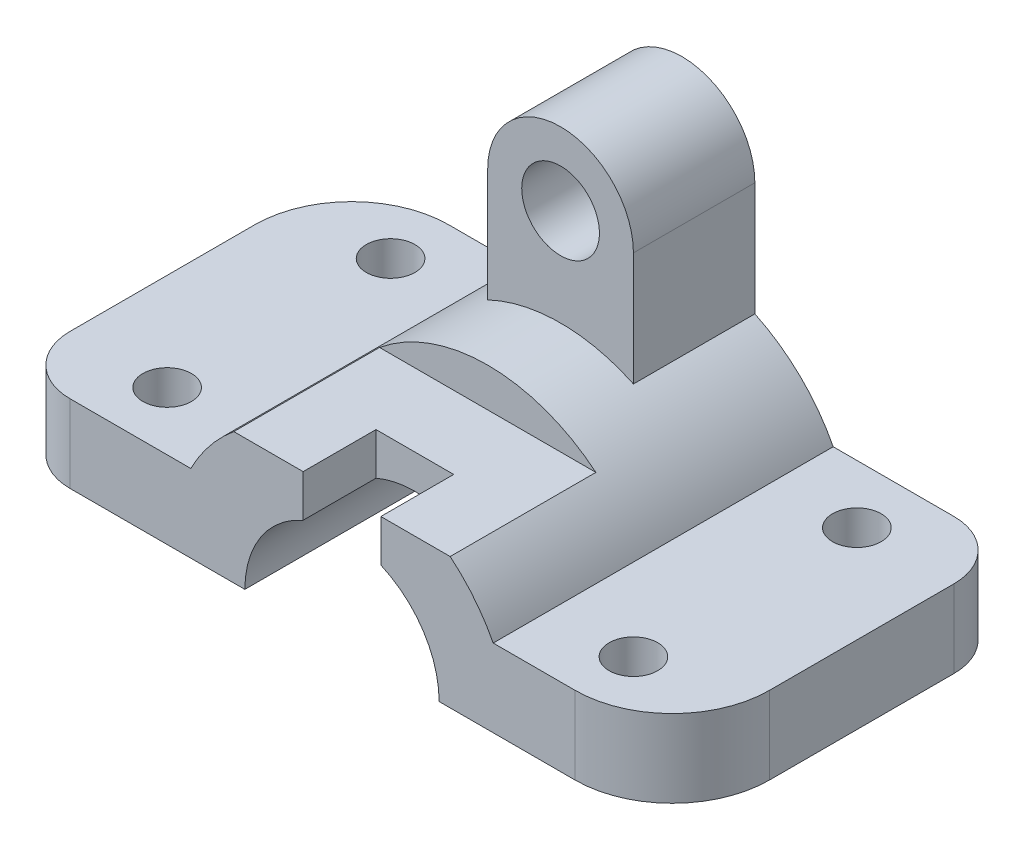
SolidWorks part; units mm, degrees
ref_plane "前视基准面" through (0, 0, 0) normal (0, 0, 1) x (1, 0, 0)
ref_plane "上视基准面" through (0, 0, 0) normal (0, 1, 0) x (1, 0, 0)
ref_plane "右视基准面" through (0, 0, 0) normal (1, 0, 0) x (0, 0, -1)
other "Configuration Table"
sketch "草图1" plane through (0, 0, 0) normal (0, 0, 1) x (1, 0, 0)
  line L0 (0, 0) -> (0, 48.6667) construction
  line L1 (-20, 0) -> (-68, 0)
  line L3 (-31.1288, 16) -> (-68, 16)
  line L4 (-68, 0) -> (-68, 16)
  line L5 (68, 0) -> (68, 16)
  line L6 (31.1288, 16) -> (68, 16)
  line L7 (20, 0) -> (68, 0)
  line L8 (-22.2711, 27) -> (22.2711, 27)
  arc A0 (-20, 0) -> (20, 0) centre (0, 0) cw
  arc A1 (-31.1288, 16) -> (31.1288, 16) centre (0, 0) cw
  dimension "D1" = 20
  dimension "D2" = 35
  dimension "D3" = 16
  dimension "D4" = 27
  dimension "D5" = 136
extrude "凸台-拉伸1" add sketch "草图1" against normal blind 70 contours A0 L0 L8 A1 L3 L4 L1 | L0 A0 L7 L5 L6 A1 L8 | L8 L0 A1 | L0 L8 A1 region at (-35.8037, 11.5512, 0) region at (35.8037, 11.5512, 0) region at (-8.4955, 30.2336, 0) region at (8.4955, 30.2336, 0)
extrude "切除-拉伸2" cut sketch "草图1<13>" against normal blind 30 contours L8 L0 A1 | L0 L8 A1 region at (-8.4955, 30.2336, 0) region at (8.4955, 30.2336, 0)
sketch "草图1<13>" plane through (0, 0, 0) normal (0, 0, 1) x (1, 0, 0) same geometry as "草图1"
sketch "草图5" plane through (0, 27, 0) normal (0, 1, 0) x (1, 0, 0)
  line L0 (-20, 0) -> (20, 0) construction
  line L1 (-8, 0) -> (8, 0)
  line L2 (-8, 0) -> (-8, 15)
  line L3 (-8, 15) -> (8, 15)
  line L4 (8, 0) -> (8, 15)
  line L5 (0, 0) -> (0, 33.0146) construction
  dimension "D1" = 16
  dimension "D2" = 15
extrude "切除-拉伸3" cut sketch "草图5" against normal through all
sketch "草图6" plane through (0, 0, -70) normal (0, 0, -1) x (-1, 0, 0)
  line L0 (-20, 0) -> (-68, 0) construction
  line L2 (-15, 31.6228) -> (-15, 55)
  line L4 (15, 31.6228) -> (15, 55)
  arc A0 (31.1288, 16) -> (-31.1288, 16) centre (0, 0) ccw construction
  arc A1 (15, 55) -> (-15, 55) centre (0, 55) ccw
  circle A2 centre (0, 55) radius 8
  arc A3 (15, 31.6228) -> (-15, 31.6228) centre (0, 0) ccw
  dimension "D1" = 15
  dimension "D2" = 16
  dimension "D3" = 55
extrude "凸台-拉伸2" add sketch "草图6" against normal blind 25
sketch "草图7" plane through (0, 16, 0) normal (0, 1, 0) x (1, 0, 0)
  line L0 (-999.7353, 35) -> (49000.2647, 35) construction
  line L1 (0, -961.6027) -> (0, 49038.3973) construction
  line L2 (68, 70) -> (68, 0) construction
  line L3 (15, 70) -> (-15, 70) construction
  circle A0 centre (-48, 12) radius 5
  circle A1 centre (-48, 58) radius 5
  circle A2 centre (48, 58) radius 5
  circle A3 centre (48, 12) radius 5
  point P3 (68, 35)
  point P5 (0, 70)
  dimension "D1" = 10
  dimension "D2" = 96
  dimension "D3" = 46
extrude "切除-拉伸4" cut sketch "草图7" against normal through all
fillet "圆角1" radius 20 2 edges at (-68, 8, -70) (68, 8, 0)
fillet "圆角2" radius 12 2 edges at (68, 8, -70) (-68, 8, 0)
